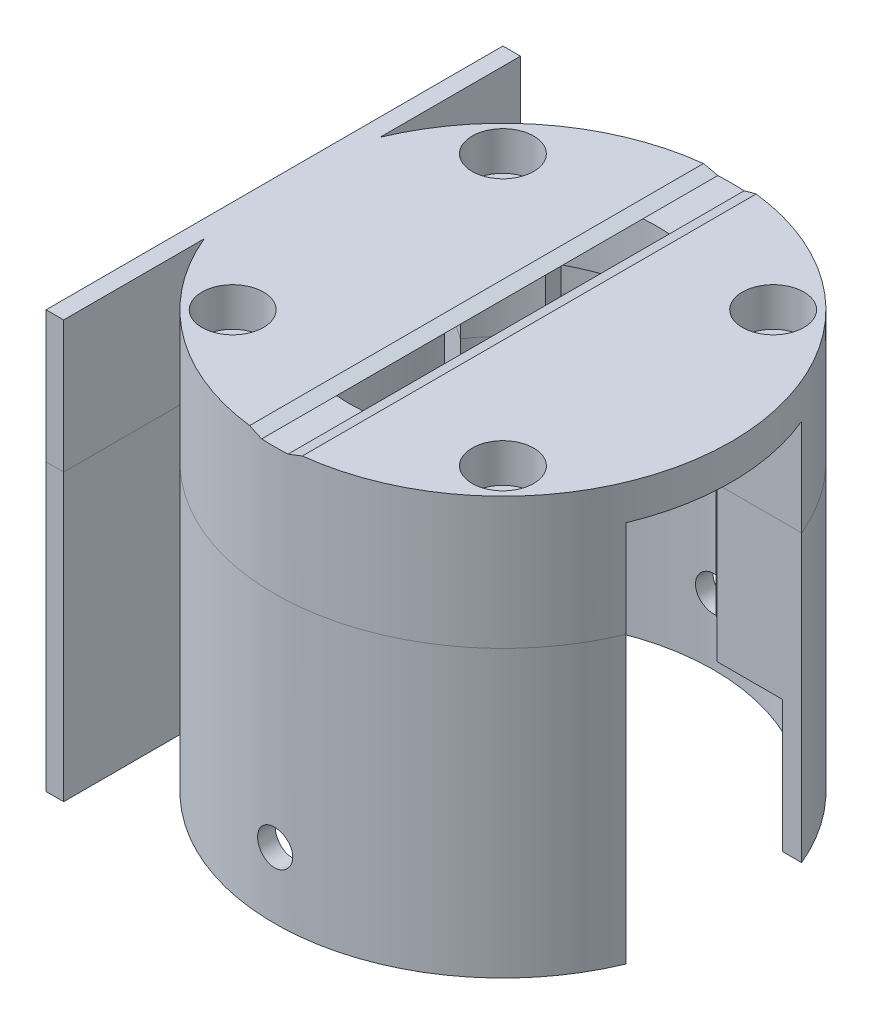
SolidWorks part; units mm, degrees
ref_plane "Front Plane" through (0, 0, 0) normal (0, 0, 1) x (1, 0, 0)
ref_plane "Top Plane" through (0, 0, 0) normal (0, 1, 0) x (1, 0, 0)
ref_plane "Right Plane" through (0, 0, 0) normal (1, 0, 0) x (0, 0, -1)
sketch "Sketch1" plane through (0, 0, 0) normal (0, 1, 0) x (1, 0, 0)
  circle A0 centre (0, 0) radius 26
  dimension "D1" = 52
extrude "Boss-Extrude1" add sketch "Sketch1" along normal blind 47
sketch "Sketch2" plane through (0, 47, 0) normal (0, 1, 0) x (1, 0, 0)
  circle A0 centre (0, 0) radius 17.5
extrude "Cut-Extrude1" cut sketch "Sketch2" against normal blind 32
sketch "Sketch3" plane through (0, 15, 0) normal (0, 1, 0) x (1, 0, 0)
  circle A0 centre (0, 0) radius 24
extrude "Cut-Extrude2" cut sketch "Sketch3" against normal through all
ref_plane "Plane1" through (26, 0, 0) normal (1, 0, 0) x (0, 0, -1)
ref_plane "Plane2" through (0, 32.5, 0) normal (0, 1, 0) x (1, 0, 0)
sketch "Sketch11" plane through (26, 0, 0) normal (1, 0, 0) x (0, 0, -1)
  line L4 (-10, 0) -> (10, 0)
  line L5 (-10, 0) -> (-10, 43.5)
  line L6 (-10, 43.5) -> (10, 43.5)
  line L7 (10, 0) -> (10, 43.5)
  line L8 (-10, 0) -> (10, 43.5) construction
  line L9 (-10, 43.5) -> (10, 0) construction
  point P0 (0, 21.75)
  point P5 (0, 0)
  dimension "D3" = 20
extrude "Cut-Extrude3" cut sketch "Sketch11" against normal blind 15
sketch "Sketch12" plane through (0, 47, 0) normal (0, 1, 0) x (1, 0, 0)
  circle A0 centre (0, 0) radius 26
extrude "Boss-Extrude2" add sketch "Sketch12" along normal blind 0.5
sketch "Sketch26" plane through (0, 0, 0) normal (0, -1, 0) x (1, 0, 0)
  line L1 (-26, 26) -> (-24, 26)
  line L2 (-26, 26) -> (-26, -26)
  line L3 (-26, -26) -> (-24, -26)
  line L4 (-24, 26) -> (-24, -26)
  dimension "D1" = 2
sketch "Sketch32" plane through (26, 0, 0) normal (1, 0, 0) x (0, 0, -1)
  line L0 (-26, 0) -> (26, 0) construction
  point P0 (0, 7.5)
  dimension "D1" = 7.5
extrude "Boss-Extrude4" add sketch "Sketch26" against normal blind 47.5
hole_wizard "Ø4.0mm Dowel Hole1" positions "Sketch32" profile "Sketch5" hole size "Ø4.0" standard "ISO"
sketch "Sketch5" plane through (26, 7.5, 0) normal (0, 1, 0) x (0, 0, -1)
  line L0 (0, 0) -> (0, 53.2017)
  line L1 (0, 53.2017) -> (2, 52)
  line L2 (2, 52) -> (2, 0)
  line L5 (2, 0) -> (0, 0)
  line L10 (0, 53.2017) -> (-2, 52) construction
  line L11 (0, -6.35) -> (0, 107.95) construction
  dimension "Hole Dia." = 4
  dimension "Hole Depth" = 52
  dimension "Drill Angle" = 118
pattern_circular "CirPattern1" count 4 over 360 about axis through (0, 0, 0) along (0, 1, 0) of "Ø4.0mm Dowel Hole1"
sketch "Sketch35" plane through (0, 0, 0) normal (0, 0, 1) x (1, 0, 0)
  line L6 (-3, 47.5) -> (3, 47.5)
  line L7 (26, 47.5) -> (-24, 47.5) construction
  line L8 (3, 47.5) -> (1.5, 47)
  line L9 (1.5, 47) -> (-1.5, 47)
  line L12 (0, -25.85) -> (0, 25.85) construction
  line L13 (-3, 47.5) -> (-1.5, 47)
  point P15 (0, 47)
  point P16 (0, 47.5)
  dimension "D1" = 6
  dimension "D2" = 3
  dimension "D3" = 0.5
extrude "Cut-Extrude5" cut sketch "Sketch35" against normal through all both and the other way through all
sketch "Sketch36" plane through (0, 47.5, 0) normal (0, 1, 0) x (1, 0, 0)
  line L0 (0, 0) -> (-15.3796, 15.3796)
  line L2 (-1.5, 25.9567) -> (-1.5, 17.4356) construction
  dimension "D1" = 21.75
  dimension "D2" = 45
hole_wizard "CBORE for M4 Hex Socket Head Cap Screw2" positions "Sketch40" profile "Sketch38" counterbore size "M4" standard "ISO" end condition through all
sketch "Sketch40" plane through (0, 47.5, 0) normal (0, 1, 0) x (1, 0, 0)
  point P0 (-15.3796, 15.3796)
sketch "Sketch38" plane through (-15.3796, 47.5, -15.3796) normal (1, 0, 0) x (0, 0, 1)
  line L0 (0, 0) -> (0, 47.5)
  line L1 (0, 47.5) -> (2, 47.5)
  line L3 (2, 47.5) -> (2, 4.4)
  line L4 (2, 4.4) -> (3.5, 4.4)
  line L5 (3.5, 4.4) -> (3.5, 0)
  line L7 (3.5, 0) -> (0, 0)
  line L11 (0, -6.35) -> (0, 107.95) construction
  dimension "Thru Hole Dia." = 4
  dimension "Thru Hole Depth" = 47.5
  dimension "C'Bore Dia." = 7
  dimension "C'Bore Depth" = 4.4
pattern_circular "CirPattern2" count 4 over 360 about axis through (0, 47.5, 0) along (0, 1, 0) of "CBORE for M4 Hex Socket Head Cap Screw2"
sketch "Sketch41" plane through (0, 15, 0) normal (0, -1, 0) x (1, 0, 0)
  line L0 (-9.7177, 14.5539) -> (-13.3272, 19.9596)
  line L1 (9.7177, 14.5539) -> (13.3272, 19.9596)
  line L2 (-9.7178, -14.5538) -> (-13.3273, -19.9595)
  line L3 (-14.5539, -9.7177) -> (-19.9596, -13.3272)
  line L4 (9.7177, -14.5539) -> (13.3272, -19.9596)
  line L5 (-14.5539, 9.7177) -> (-19.9596, 13.3272)
  arc A1 (21.8174, 10) -> (21.8174, -10) centre (0, 0) ccw construction
  arc A5 (21.8174, 10) -> (21.8174, -10) centre (0, 0) ccw construction
  arc A6 (-9.7178, -14.5538) -> (9.7177, -14.5539) centre (0, 0) ccw
  arc A7 (-13.3273, -19.9595) -> (13.3272, -19.9596) centre (0, 0) ccw
  arc A8 (-19.9596, 13.3272) -> (-19.9596, -13.3272) centre (0, 0) ccw
  arc A9 (-14.5539, 9.7177) -> (-14.5539, -9.7177) centre (0, 0) ccw
  arc A10 (9.7177, 14.5539) -> (-9.7177, 14.5539) centre (0, 0) ccw
  arc A11 (13.3272, 19.9596) -> (-13.3272, 19.9596) centre (0, 0) ccw
extrude "Cut-Extrude6" cut sketch "Sketch41" against normal blind 25
split "Split2" trim tools "Plane2" bodies to split 136 135 resulting bodies 137 138
